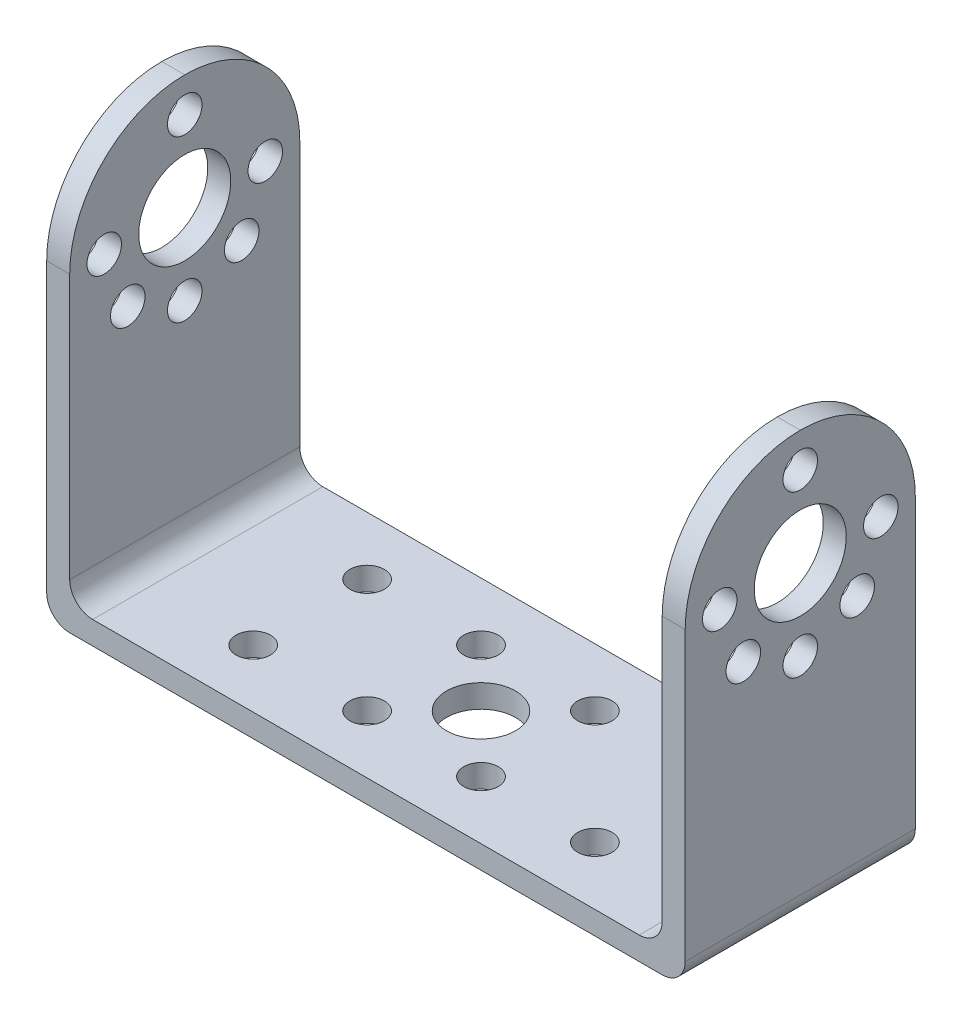
SolidWorks part; units mm, degrees
ref_plane "Спереди" through (0, 0, 0) normal (0, 0, 1) x (1, 0, 0)
ref_plane "Сверху" through (0, 0, 0) normal (0, 1, 0) x (1, 0, 0)
ref_plane "Справа" through (0, 0, 0) normal (1, 0, 0) x (0, 0, -1)
sketch "Sketch2" plane through (0, 0, 0) normal (0, 0, 1) x (1, 0, 0)
  line L0 (0, 0) -> (55.5, 0)
  line L3 (2, 2) -> (53.5, 2)
  line L4 (0, 37) -> (0, 0)
  line L5 (55.5, 0) -> (55.5, 37)
  line L6 (55.5, 37) -> (53.5, 37)
  line L7 (53.5, 37) -> (53.5, 2)
  line L8 (2, 37) -> (2, 2)
  line L9 (0, 37) -> (2, 37)
  dimension "D1" = 55.5
  dimension "D2" = 37
  dimension "D3" = 2
  dimension "D4" = 2
  dimension "D5" = 2
  dimension "D6" = 35
  dimension "D7" = 35
extrude "Основа" add sketch "Sketch2" along normal blind 20 contours L4 L0 L3 L8 L9 | L6 L7 L3 L0 L5 region at (0.667, 18.5, 0)
sketch "Sketch6" plane through (0, 0, 0) normal (0, -1, 0) x (-1, 0, 0)
  line L0 (0, 0) -> (-27.75, 0) construction
  line L1 (0, 0) -> (-55.5, 0) construction
  line L2 (-27.75, 0) -> (-27.75, -10) construction
  line L3 (-32.6997, -5.0503) -> (-27.75, -10) construction
  line L4 (-27.75, -10) -> (-32.6997, -10) construction
  circle A0 centre (-27.75, -10) radius 3
  circle A1 centre (-32.6997, -14.9497) radius 1.5
  circle A2 centre (-32.6997, -5.0503) radius 1.5
  circle A3 centre (-42.5997, -14.9497) radius 1.5
  circle A4 centre (-42.5997, -5.0503) radius 1.5
  circle A5 centre (-12.9003, -5.0503) radius 1.5
  circle A6 centre (-22.8003, -5.0503) radius 1.5
  circle A7 centre (-22.8003, -14.9497) radius 1.5
  circle A8 centre (-12.9003, -14.9497) radius 1.5
  point P20 (-27.75, -10)
  dimension "D1" = 6
  dimension "D2" = 7
  dimension "D3" = 10
  dimension "D5" = 3
  dimension "D7" = 9.9
  dimension "D6" = 2
  dimension "D8" = 5.0503
  dimension "D4" = 45
extrude "Центральные отверстия под крепёж" cut sketch "Sketch6" against normal blind 70
sketch "Sketch7" plane through (0, 0, 0) normal (-1, 0, 0) x (0, 0, 1)
  line L0 (0, 0) -> (0, 37) construction
  line L1 (0, 37) -> (10, 37) construction
  line L2 (20, 37) -> (0, 37) construction
  line L3 (10, 37) -> (10, 27) construction
  line L4 (3, 27) -> (10, 27) construction
  circle A0 centre (14.9497, 31.9497) radius 1.5 [skipped]
  circle A1 centre (17, 27) radius 1.5
  circle A2 centre (14.9497, 22.0503) radius 1.5
  circle A3 centre (10, 20) radius 1.5
  circle A4 centre (5.0503, 22.0503) radius 1.5
  circle A5 centre (10, 34) radius 1.5
  circle A6 centre (3, 27) radius 1.5
  circle A7 centre (5.0503, 31.9497) radius 1.5 [skipped]
  circle A8 centre (10, 27) radius 4
  point P27 (10, 27)
  dimension "D3" = 3
  dimension "D5" = 7
  dimension "D6" = 8
  dimension "D1" = 10
  dimension "D2" = 3
  dimension "D4" = 8
extrude "Боковые отверстия под крепёж" cut sketch "Sketch7" against normal blind 55.5
fillet "Fillet1" radius 10 4 edges at (54.5, 37, 20) (54.5, 37, 0) (1, 37, 0) (1, 37, 20)
fillet "Fillet2" radius 2 4 edges at (0, 0, 10) (55.5, 0, 10) (2, 2, 10) (53.5, 2, 10)
sketch "Эскиз1" plane through (0, 0, 0) normal (0, -1, 0) x (1, 0, 0)
  line L0 (42.5997, 5.0503) -> (32.6997, 5.0503)
  line L1 (32.6997, 5.0503) -> (22.8003, 5.0503)
  line L2 (22.8003, 5.0503) -> (12.9003, 5.0503)
  line L3 (12.9003, 5.0503) -> (12.9003, 14.9497)
  line L4 (12.9003, 14.9497) -> (22.8003, 14.9497)
  line L5 (22.8003, 14.9497) -> (32.6997, 14.9497)
  line L6 (32.6997, 14.9497) -> (42.5997, 14.9497)
  line L7 (42.5997, 14.9497) -> (42.5997, 5.0503)
